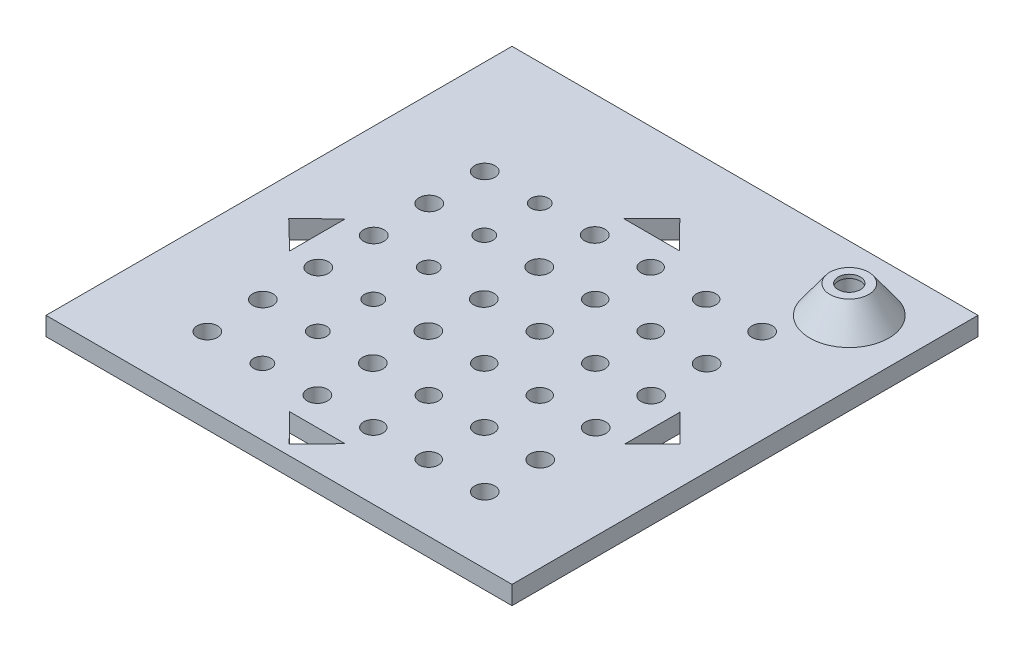
SolidWorks part; units mm, degrees
ref_plane "Front Plane" through (0, 0, 0) normal (0, 0, 1) x (1, 0, 0)
ref_plane "Top Plane" through (0, 0, 0) normal (0, 1, 0) x (1, 0, 0)
ref_plane "Right Plane" through (0, 0, 0) normal (1, 0, 0) x (0, 0, -1)
sketch "Sketch1" plane through (0, 0, 0) normal (0, 1, 0) x (1, 0, 0)
  line L1 (0, 0) -> (126, 0)
  line L2 (0, 0) -> (0, 126)
  line L3 (0, 126) -> (126, 126)
  line L4 (126, 0) -> (126, 126)
  dimension "D1" = 126
  dimension "D2" = 126
extrude "Boss-Extrude1" add sketch "Sketch1" along normal blind 5
sketch "Sketch3" plane through (0, 5, 0) normal (0, 1, 0) x (1, 0, 0)
  line L0 (108.6, 121.1) -> (108.6, 96.1) construction
  circle A0 centre (108.6, 108.6) radius 12.5
extrude "Boss-Extrude2" add sketch "Sketch3" along normal blind 7.5
sketch "Sketch4" plane through (0, 0, 0) normal (0, -1, 0) x (1, 0, 0)
  circle A1 centre (108.6, -108.6) radius 3.45
  dimension "D1" = 6.9
extrude "Cut-Extrude1" cut sketch "Sketch4" against normal blind 11.5
sketch "Sketch6" plane through (0, 12.5, 0) normal (0, 1, 0) x (1, 0, 0)
  line L0 (108.6, 121.1) -> (108.6, 96.1) construction
  circle A0 centre (108.6, 108.6) radius 12.5 construction
  circle A1 centre (108.6, 108.6) radius 3
  dimension "D1" = 6
extrude "Cut-Extrude2" cut sketch "Sketch6" against normal through all
chamfer "Chamfer1" distance 10 angle 36 1 edges at (108.6, 12.5, -96.1) first distance on face at (108.6, 12.5, -96.1)
sketch "Sketch7" plane through (0, 5, 0) normal (0, 1, 0) x (1, 0, 0)
  line L0 (94.5, 63) -> (94.5, 126) construction
  line L1 (126, 126) -> (0, 126) construction
  line L2 (0, 0) -> (126, 0) construction
  line L3 (31.5, 63) -> (31.5, 0) construction
  line L4 (55.375, 60.25) -> (55.375, 50.75) construction
  line L5 (63, 63) -> (58.125, 63) construction
  line L6 (63, 63) -> (67.875, 63) construction
  line L7 (31.5, 63) -> (31.5, 126) construction
  line L8 (52.625, 63) -> (42.875, 63) construction
  line L9 (55.375, 45.25) -> (55.375, 35.75) construction
  line L10 (63, 63) -> (63, 126) construction
  line L11 (63, 63) -> (63, 0) construction
  line L12 (94.5, 63) -> (94.5, 0) construction
  line L13 (73.125, 63) -> (82.875, 63) construction
  line L14 (88.125, 63) -> (97.875, 63) construction
  line L15 (38.125, 63) -> (28.375, 63) construction
  line L16 (55.375, 30.25) -> (55.375, 20.75) construction
  line L17 (55.375, 75.25) -> (55.375, 65.75) construction
  circle A0 centre (55.375, 63) radius 2.75
  circle A1 centre (70.5, 63) radius 2.625
  circle A2 centre (40.5, 63) radius 2.375
  circle A3 centre (85.5, 63) radius 2.625
  circle A4 centre (25.625, 63) radius 2.75
  circle A5 centre (100.625, 63) radius 2.75
  circle A6 centre (25.625, 48) radius 2.75
  circle A7 centre (40.5, 48) radius 2.375
  circle A8 centre (55.375, 48) radius 2.75
  circle A9 centre (70.5, 48) radius 2.625
  circle A10 centre (85.5, 48) radius 2.625
  circle A11 centre (100.625, 48) radius 2.75
  circle A12 centre (25.625, 33) radius 2.75
  circle A13 centre (40.5, 33) radius 2.375
  circle A14 centre (55.375, 33) radius 2.75
  circle A15 centre (70.5, 33) radius 2.625
  circle A16 centre (85.5, 33) radius 2.625
  circle A17 centre (100.625, 33) radius 2.75
  circle A18 centre (25.625, 18) radius 2.75
  circle A19 centre (40.5, 18) radius 2.375
  circle A20 centre (55.375, 18) radius 2.75
  circle A21 centre (70.5, 18) radius 2.625
  circle A22 centre (85.5, 18) radius 2.625
  circle A23 centre (100.625, 18) radius 2.75
  circle A24 centre (25.625, 78) radius 2.75
  circle A25 centre (40.5, 78) radius 2.375
  circle A26 centre (55.375, 78) radius 2.75
  circle A27 centre (70.5, 78) radius 2.625
  circle A28 centre (85.5, 78) radius 2.625
  circle A29 centre (100.625, 78) radius 2.75
  circle A30 centre (25.625, 93) radius 2.75
  circle A31 centre (40.5, 93) radius 2.375
  circle A32 centre (55.375, 93) radius 2.75
  circle A33 centre (70.5, 93) radius 2.625
  circle A34 centre (85.5, 93) radius 2.625
  circle A35 centre (100.625, 93) radius 2.75
  dimension "D1" = 5.5
  dimension "D2" = 4.875
  dimension "D3" = 4.875
  dimension "D4" = 9.75
  dimension "D5" = 9.75
  dimension "D6" = 9.75
  dimension "D7" = 9.75
  dimension "D9" = 9.5
  dimension "D10" = 3
  dimension "D11" = 9.5
  dimension "D8" = 4
extrude "Cut-Extrude3" cut sketch "Sketch7" against normal through all
sketch "Sketch8" plane through (0, 5, 0) normal (0, 1, 0) x (1, 0, 0)
  line L0 (22.875, 63) -> (17.875, 63) construction
  line L1 (103.375, 63) -> (108.375, 63) construction
  line L2 (55.4999, 95.7472) -> (55.4999, 100.7472) construction
  line L3 (70.5, 15.375) -> (70.5, 10.375) construction
  line L4 (70.5, 100.7472) -> (63, 108.375)
  line L14 (108.375, 63) -> (115.875, 55.5)
  line L17 (55.5, 10.375) -> (63, 2.75)
  line L18 (63, 2.75) -> (63, 10.375) construction
  line L21 (70.5, 100.7472) -> (55.4999, 100.7472)
  line L24 (17.875, 63) -> (17.875, 48)
  line L39 (55.5, 10.375) -> (70.5, 10.375)
  line L42 (17.875, 63) -> (10.125, 55.5)
  line L43 (70.5, 10.375) -> (63, 2.75)
  line L46 (55.4999, 100.7472) -> (63, 108.375)
  line L48 (17.875, 48) -> (10.125, 55.5)
  line L49 (108.375, 63) -> (108.375, 48)
  line L52 (108.375, 48) -> (115.875, 55.5)
  circle A0 centre (25.625, 63) radius 2.75 construction
  circle A1 centre (100.625, 63) radius 2.75 construction
  circle A2 centre (55.375, 93) radius 2.75 construction
  circle A3 centre (70.5, 18) radius 2.625 construction
  point P15 (63, 103.375)
  point P24 (114.625, 55.5)
  point P47 (63, 8.9645)
  dimension "D1" = 7.625
  dimension "D2" = 5
  dimension "D3" = 5
  dimension "D4" = 5
  dimension "D5" = 5
extrude "Cut-Extrude4" cut sketch "Sketch8" against normal through all
